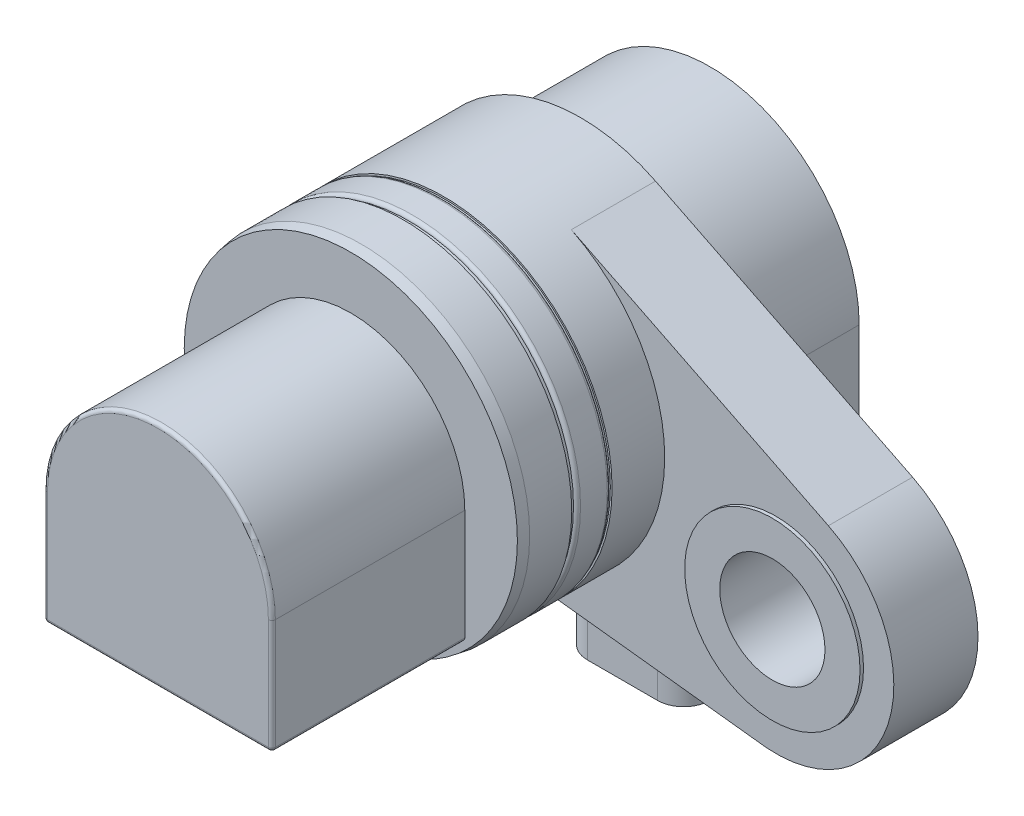
SolidWorks part; units mm, degrees
ref_plane "正面" through (0, 0, 0) normal (0, 0, 1) x (1, 0, 0)
ref_plane "平面" through (0, 0, 0) normal (0, 1, 0) x (1, 0, 0)
ref_plane "右側面" through (0, 0, 0) normal (1, 0, 0) x (0, 0, -1)
sketch "ｽｹｯﾁ1" plane through (0, 0, 0) normal (0, 0, 1) x (1, 0, 0)
  line L0 (0, 0) -> (17, 0)
  line L1 (0, 0) -> (0, 12.5)
  line L2 (17, 0) -> (17, 12.5)
  arc A0 (0, 12.5) -> (17, 12.5) centre (8.5, 12.5) cw
extrude "ﾎﾞｽ - 押し出し1" add sketch "ｽｹｯﾁ1" along normal blind 7.4 contours A0 L2 L0 L1
sketch "ｽｹｯﾁ2" plane through (0, 0, 7.4) normal (0, 0, 1) x (1, 0, 0)
  line L0 (7.4218, 3.0567) -> (23.9646, 1.1679)
  line L1 (12.7852, 21.1907) -> (27.445, 13.901)
  arc A0 (12.7852, 21.1907) -> (7.4218, 3.0567) centre (8.5108, 12.5947) ccw
  arc A1 (23.9646, 1.1679) -> (27.445, 13.901) centre (24.4498, 7.8775) ccw
  point P0 (0, 8)
  point P8 (17, 2)
  dimension "D2" = 9.6
  dimension "D1" = 8
extrude "ﾎﾞｽ - 押し出し2" add sketch "ｽｹｯﾁ2" along normal blind 4.8 contours L1 A1 L0 A0
sketch "ｽｹｯﾁ3" plane through (0, 0, 12.2) normal (0, 0, 1) x (1, 0, 0)
  circle A2 centre (8.5108, 12.5947) radius 9.6
extrude "ﾎﾞｽ - 押し出し3" add sketch "ｽｹｯﾁ3" along normal blind 3
sketch "ｽｹｯﾁ6" plane through (0, 0, 15.2) normal (0, 0, 1) x (1, 0, 0)
  line L0 (18.1108, 12.5947) -> (-1.0892, 12.5947)
  circle A1 centre (8.5108, 12.5947) radius 9.5
extrude "ﾎﾞｽ - 押し出し4" add sketch "ｽｹｯﾁ6" along normal blind 0.1 contours A1
sketch "ｽｹｯﾁ7" plane through (0, 0, 15.3) normal (0, 0, 1) x (1, 0, 0)
  line L0 (18.0108, 12.5947) -> (-0.9892, 12.5947)
  circle A0 centre (8.5108, 12.5947) radius 9.6
extrude "ﾎﾞｽ - 押し出し6" add sketch "ｽｹｯﾁ7" along normal blind 1.9 contours A0
fillet "ﾌｨﾚｯﾄ1" radius 0.2 1 edges at (18.1108, 12.5947, 15.3)
fillet "ﾌｨﾚｯﾄ2" radius 0.2 1 edges at (18.1108, 12.5947, 17.2)
sketch "ｽｹｯﾁ8" plane through (0, 0, 17.2) normal (0, 0, 1) x (1, 0, 0)
  circle A0 centre (8.5108, 12.5947) radius 9.4
extrude "ﾎﾞｽ - 押し出し7" add sketch "ｽｹｯﾁ8" along normal blind 0.3
sketch "ｽｹｯﾁ9" plane through (0, 0, 17.5) normal (0, 0, 1) x (1, 0, 0)
  circle A0 centre (8.5108, 12.5947) radius 9.6
extrude "ﾎﾞｽ - 押し出し8" add sketch "ｽｹｯﾁ9" along normal blind 3 contours A0
chamfer "面取り1" distance 0.6 distance2 0.1 1 edges at (18.1108, 12.5947, 20.5) first distance on face at (18.1108, 12.5947, 20.5)
sketch "ｽｹｯﾁ10" plane through (0, 0, 20.5) normal (0, 0, 1) x (1, 0, 0)
  line L0 (15.0108, 6.0947) -> (15.0108, 12.5947)
  line L1 (15.0108, 6.0947) -> (2.0108, 6.0947)
  line L2 (2.0108, 6.0947) -> (2.0108, 12.5947)
  arc A0 (2.0108, 12.5947) -> (15.0108, 12.5947) centre (8.5108, 12.5947) cw
  dimension "D2" = 13
  dimension "D3" = 6.5
extrude "ﾎﾞｽ - 押し出し9" add sketch "ｽｹｯﾁ10" along normal blind 11
fillet "ﾌｨﾚｯﾄ3" radius 0.2 2 edges at (15.0108, 6.0947, 26) (2.0108, 6.0947, 26)
fillet "ﾌｨﾚｯﾄ4" radius 0.2 6 edges at (2.0694, 6.1533, 31.5) (2.0108, 9.4447, 31.5) (8.5108, 19.0947, 31.5) (15.0108, 9.4447, 31.5) (14.9522, 6.1533, 31.5) (8.5108, 6.0947, 31.5)
sketch "ｽｹｯﾁ12" plane through (0, 0, 12.2) normal (0, 0, 1) x (1, 0, 0)
  circle A0 centre (24.4498, 7.8775) radius 5
  circle A1 centre (24.4498, 7.8775) radius 3
extrude "ﾎﾞｽ - 押し出し11" add sketch "ｽｹｯﾁ12" along normal blind 0.2 contours A0 | A1
sketch "ｽｹｯﾁ23" plane through (0, 0, 7.4) normal (0, 0, -1) x (-1, 0, 0)
  circle A0 centre (-24.4498, 7.8775) radius 5
  circle A1 centre (-24.4498, 7.8775) radius 3
extrude "ﾎﾞｽ - 押し出し12" add sketch "ｽｹｯﾁ23" along normal blind 0.2
sketch "ｽｹｯﾁ26" plane through (0, 0, 12.2) normal (0, 0, 1) x (1, 0, 0)
  circle A0 centre (24.4498, 7.8775) radius 3
extrude "ｶｯﾄ - 押し出し2" cut sketch "ｽｹｯﾁ26" against normal blind 7.4
sketch "ｽｹｯﾁ27" plane through (0, 0, 0) normal (0, -1, 0) x (1, 0, 0)
  line L1 (15, 0) -> (2, 0)
  line L2 (15, 0) -> (15, 7)
  line L3 (15, 7) -> (2, 7)
  line L4 (2, 0) -> (2, 7)
  point P0 (15, 0)
  point P2 (2, 0)
  dimension "D1" = 2
  dimension "D2" = 2
extrude "ﾎﾞｽ - 押し出し13" add sketch "ｽｹｯﾁ27" along normal blind 1.8 contours L3 L4 L1 L2
fillet "ﾌｨﾚｯﾄ5" radius 2 2 edges at (0, 0, 3.7) (17, 0, 3.7)
sketch "ｽｹｯﾁ28" plane through (0, -1.8, 0) normal (0, -1, 0) x (-1, 0, 0)
  line L0 (-15, -1) -> (-2, -1)
  line L1 (-15, 0) -> (-2, 0) construction
  line L2 (-15, -5) -> (-2, -5)
  line L3 (-15, -7) -> (-2, -7) construction
  line L4 (-12, -5) -> (-12, -1)
  line L5 (-15, 0) -> (-15, -7) construction
  line L6 (-5, -5) -> (-5, -1)
  line L7 (-2, 0) -> (-2, -7) construction
  line L9 (-5, -1) -> (-12, -1)
  line L10 (-5, -1) -> (-5, -5)
  line L11 (-5, -5) -> (-12, -5)
  line L12 (-12, -1) -> (-12, -5)
  dimension "D1" = 1
  dimension "D2" = 2
  dimension "D3" = 3
  dimension "D4" = 3
extrude "ﾎﾞｽ - 押し出し14" add sketch "ｽｹｯﾁ28" along normal blind 5 contours L2 L6 L0 L4 region at (8.5, -1.8, 3)
fillet "ﾌｨﾚｯﾄ6" radius 1 2 edges at (2, -0.9, 7) (15, -0.9, 7)
fillet "ﾌｨﾚｯﾄ7" radius 1.5 4 edges at (12, -4.3, 1) (12, -4.3, 5) (5, -4.3, 1) (5, -4.3, 5)
sketch "ｽｹｯﾁ29" plane through (0, 0, 0) normal (0, 0, -1) x (-1, 0, 0)
  line L1 (-15, -1.8) -> (-2, -1.8)
  line L2 (-15, -1.8) -> (-15, 1.7686)
  line L3 (-15, 1.7686) -> (-2, 1.7686)
  line L4 (-2, -1.8) -> (-2, 1.7686)
extrude "ﾎﾞｽ - 押し出し15" add sketch "ｽｹｯﾁ29" along normal blind 0.3 contours L3 L4 L1 L2
sketch "ｽｹｯﾁ30" plane through (0, -6.8, 0) normal (0, -1, 0) x (1, 0, 0)
  line L0 (10, 3) -> (7, 3) construction
  line L1 (8.5, 1) -> (8.5, 5) construction
  line L2 (10.5, 1) -> (6.5, 1) construction
  line L3 (10.5, 5) -> (6.5, 5) construction
  circle A0 centre (8.5, 3) radius 0.75
  circle A1 centre (10, 3) radius 0.75
  circle A2 centre (7, 3) radius 0.75
  dimension "D1" = 1.5
extrude "ｶｯﾄ - 押し出し3" cut sketch "ｽｹｯﾁ30" against normal blind 0.5 contours A1 | A2 region at (7, -6.8, 3) region at (10, -6.8, 3)
sketch "ｽｹｯﾁ31" plane through (0, -6.8, 0) normal (0, -1, 0) x (1, 0, 0)
  circle A0 centre (8.5, 3) radius 0.65
  circle A1 centre (7, 3) radius 0.75
  circle A2 centre (7, 3) radius 0.75
  circle A3 centre (10, 3) radius 0.75
  circle A4 centre (10, 3) radius 0.75
  circle A5 centre (8.5, 3) radius 0.75
  circle A6 centre (8.5, 3) radius 0.75
  dimension "D1" = 0
  dimension "D2" = 0
  dimension "D3" = 0
  dimension "D4" = 0.1
extrude "ｶｯﾄ - 押し出し5" cut sketch "ｽｹｯﾁ31" against normal up to surface (0.5 mm away) contours A0 up to face at (10, -6.3, 2.25)
